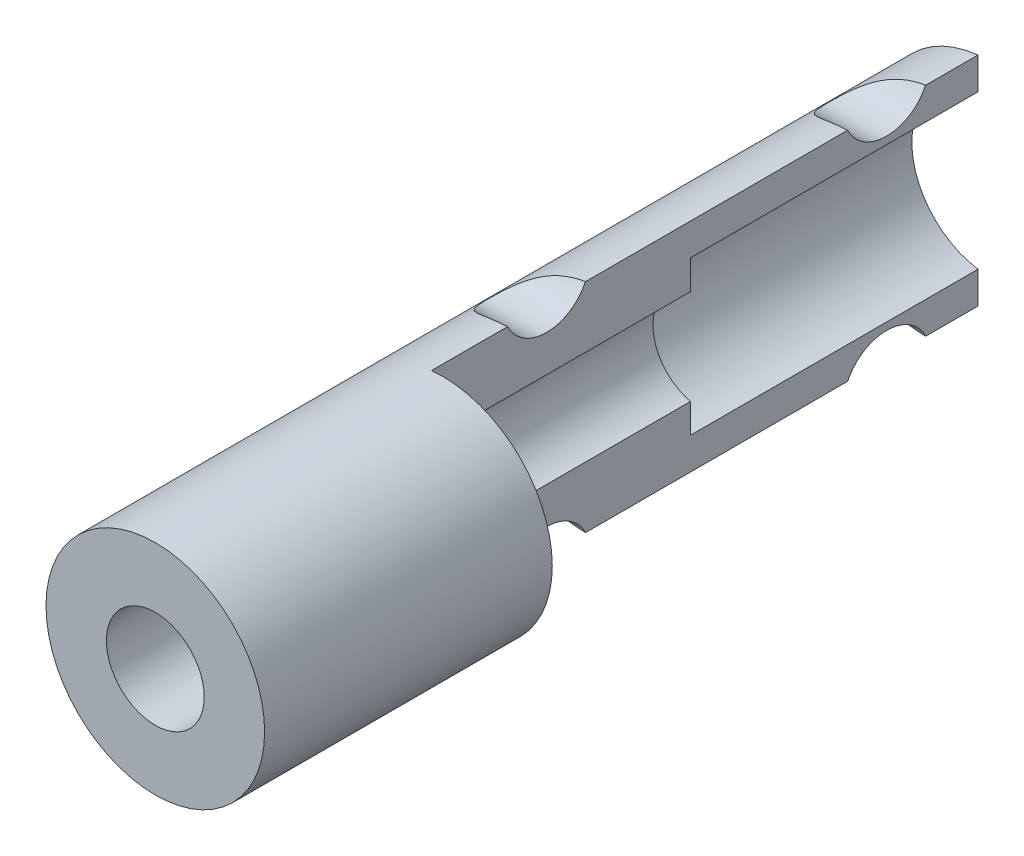
SolidWorks part; units mm, degrees
ref_plane "Front Plane" through (0, 0, 0) normal (0, 0, 1) x (1, 0, 0)
ref_plane "Top Plane" through (0, 0, 0) normal (0, 1, 0) x (1, 0, 0)
ref_plane "Right Plane" through (0, 0, 0) normal (1, 0, 0) x (0, 0, -1)
sketch "Sketch1" plane through (0, 0, 0) normal (0, 0, 1) x (1, 0, 0)
  circle A0 centre (0, 0) radius 3.8
  circle A1 centre (0, 0) radius 1.7
extrude "Extrude1" add sketch "Sketch1" along normal blind 10
sketch "Sketch2" plane through (0, 0, 0) normal (0, 0, -1) x (-1, 0, 0)
  line L0 (0, 3.8) -> (0, 1.7)
  line L1 (0, -1.7) -> (0, -3.8)
  arc A0 (0, 3.8) -> (0, -3.8) centre (0, 0) cw
  circle A1 centre (0, 0) radius 3.8 construction
  arc A2 (0, 1.7) -> (0, -1.7) centre (0, 0) cw
  circle A3 centre (0, 0) radius 1.7 construction
extrude "Extrude2" add sketch "Sketch2" along normal blind 9
sketch "Sketch3" plane through (0, 0, -9) normal (0, 0, -1) x (-1, 0, 0)
  line L0 (0, 3.8) -> (0, 2.7)
  line L1 (0, -2.7) -> (0, -3.8)
  arc A0 (0, 3.8) -> (0, -3.8) centre (0, 0) cw
  arc A1 (0, 3.8) -> (0, -3.8) centre (0, 0) ccw construction
  circle A2 centre (0, 0) radius 2.7 construction
  arc A3 (0, 2.7) -> (0, -2.7) centre (0, 0) cw
extrude "Extrude3" add sketch "Sketch3" along normal blind 10
sketch "Sketch4" plane through (0, 0, 0) normal (1, 0, 0) x (0, 0, -1)
  line L0 (15.825, -7.9375) -> (15.825, 7.9375) construction
  line L1 (4, -9.525) -> (4, 9.525) construction
  line L2 (-1.5875, 4.425) -> (19.05, 4.425) construction
  line L3 (19.05, -4.425) -> (-3.175, -4.425) construction
  line L4 (19, -2.7) -> (19, 2.7) construction
  line L5 (0, -3.8) -> (0, 3.8) construction
  circle A0 centre (4, 4.425) radius 1.5
  circle A1 centre (15.825, 4.425) radius 1.5
  circle A2 centre (15.825, -4.425) radius 1.5
  circle A3 centre (4, -4.425) radius 1.5
  dimension "D1" = 3.175
  dimension "D2" = 4
  dimension "D3" = 4.425
  dimension "D4" = 4.425
extrude "Extrude4" cut sketch "Sketch4" against normal blind 17
sketch "Sketch5" plane through (0, 0, -19) normal (0, 0, -1) x (-1, 0, 0)
  line L0 (0.4, 4.7625) -> (0.4, -4.7625) construction
  line L1 (0, 4.7625) -> (0, -4.7625)
  line L2 (0, -4.7625) -> (0.4, -4.7625)
  line L3 (0.4, -4.7625) -> (0.4, 4.7625)
  line L4 (0.4, 4.7625) -> (0, 4.7625)
  dimension "D1" = 0.4
extrude "Extrude5" cut sketch "Sketch5" against normal up to surface (19 mm away) up to face at (0, -0.85, 0)
